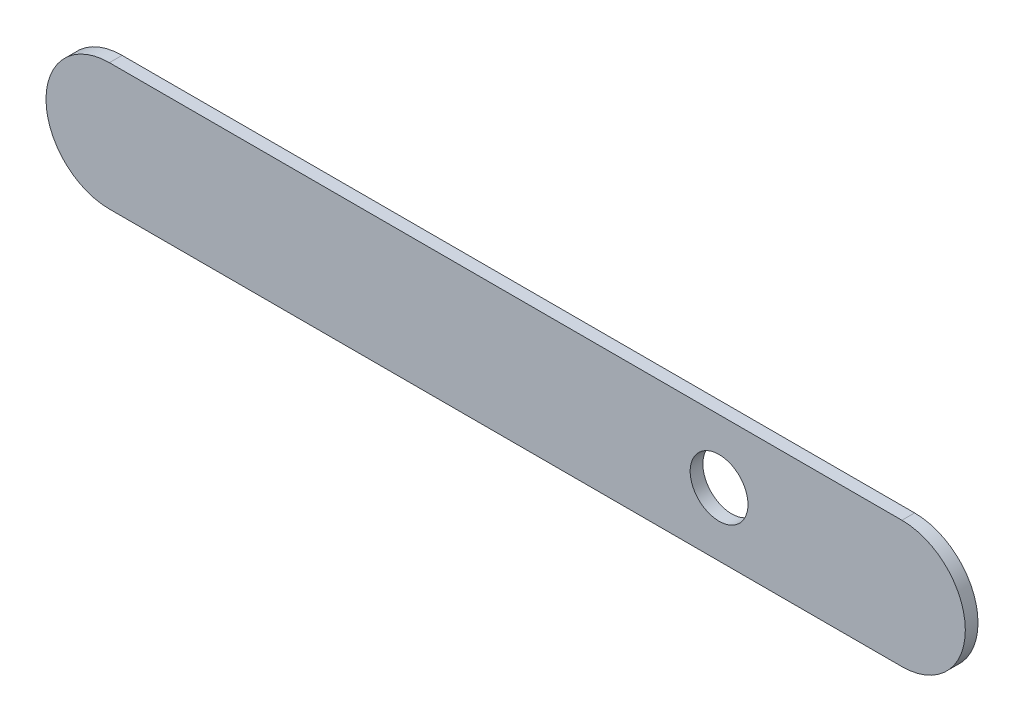
SolidWorks part; units mm, degrees
ref_plane "Front Plane" through (0, 0, 0) normal (0, 0, 1) x (1, 0, 0)
ref_plane "Top Plane" through (0, 0, 0) normal (0, 1, 0) x (1, 0, 0)
ref_plane "Right Plane" through (0, 0, 0) normal (1, 0, 0) x (0, 0, -1)
sketch "Sketch1" plane through (0, 0, 0) normal (0, 0, 1) x (1, 0, 0)
  line L0 (0, 0) -> (125, 0) construction
  line L1 (0, 10) -> (125, 10)
  line L2 (0, -10) -> (125, -10)
  arc A0 (0, 10) -> (0, -10) centre (0, 0) ccw
  arc A1 (125, -10) -> (125, 10) centre (125, 0) ccw
  circle A2 centre (96.159, 0) radius 4.5581
  point P3 (62.5, 0)
  point P10 (96.159, 0)
  dimension "D1" = 10
  dimension "D2" = 125
extrude "Boss-Extrude1" add sketch "Sketch1" along normal mid plane 2
